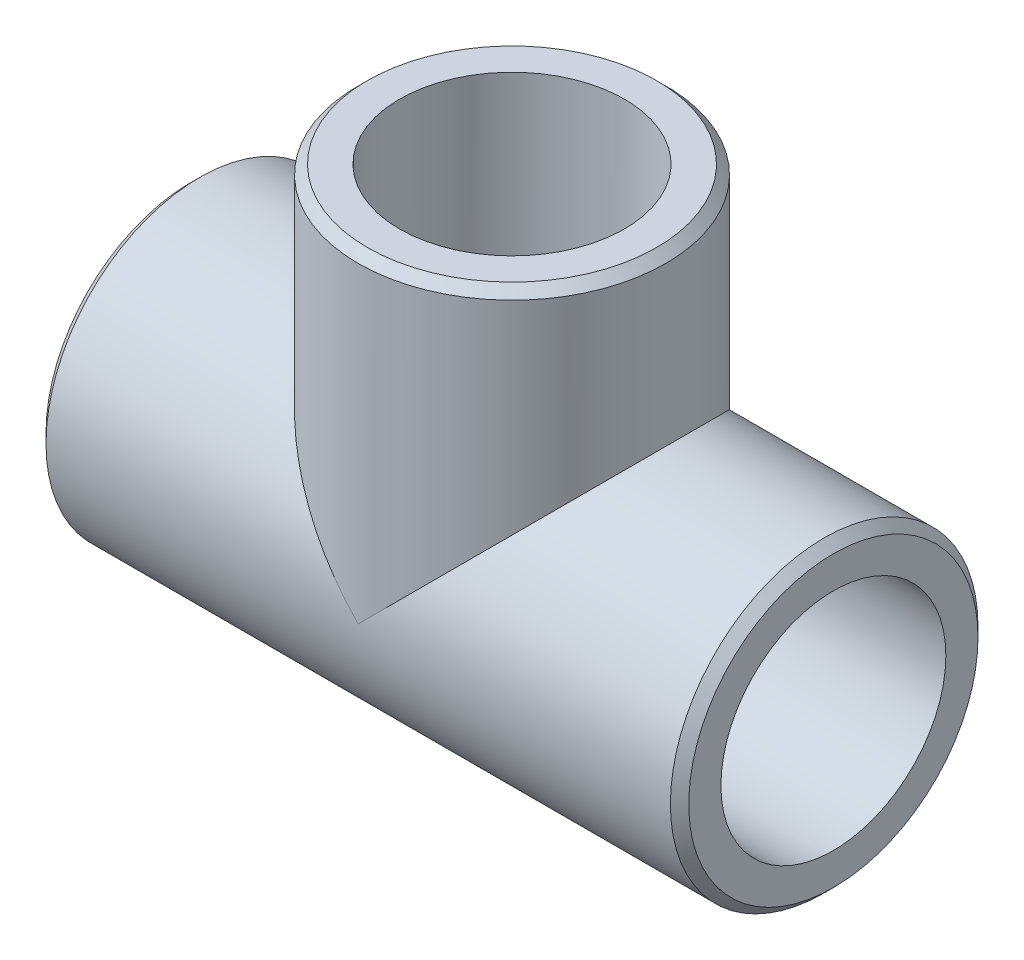
SolidWorks part; units mm, degrees
ref_plane "Спереди" through (0, 0, 0) normal (0, 0, 1) x (1, 0, 0)
ref_plane "Сверху" through (0, 0, 0) normal (0, 1, 0) x (1, 0, 0)
ref_plane "Справа" through (0, 0, 0) normal (1, 0, 0) x (0, 0, -1)
sketch "RunRoute" plane through (0, 0, 0) normal (1, 0, 0) x (0, 0, -1)
  circle A0 centre (0, 0) radius 16.75
  dimension "Diameter" = 33.5
extrude "RunExtrude" add sketch "RunRoute" along normal blind 35
mirror "RunExtrudeMirror" about plane through (0, 0, 0) normal (1, 0, 0) of "RunExtrude"
sketch "OutletRoute" plane through (0, 0, 0) normal (0, 1, 0) x (1, 0, 0)
  circle A0 centre (0, 0) radius 16.75
  dimension "Diameter" = 33.5
extrude "OutletExtrude" add sketch "OutletRoute" along normal blind 35
shell "TeeShell" thickness 4.5 removed face at (-35, 0, -16.75) removed face at (35, 0, -16.75) removed face at (0, 35, 16.75)
chamfer "TeeChamfer" distance 1 angle 45 3 edges at (35, 0, -16.75) (-35, 0, -16.75) (0, 35, 16.75)
sketch "Sketch1" plane through (0, 0, 0) normal (0, 0, 1) x (1, 0, 0)
  line L0 (-35, 0) -> (35, 0) construction
  line L1 (-35, 15.75) -> (-35, -15.75) construction
  line L2 (35, -15.75) -> (35, 15.75) construction
  line L3 (0, 0) -> (0, 35) construction
  line L4 (12.25, 35) -> (-12.25, 35) construction
other "CPoint1" parameters "Diameter"=25, "StubLength"=0
ref_axis "Axis1" through (45, 0, 0) along (-1, 0, 0)
other "CPoint2" parameters "Diameter"=25, "StubLength"=0
ref_axis "Axis2" through (0, 45, 0) along (0, -1, 0)
other "CPoint3" parameters "Diameter"=25, "StubLength"=0
ref_axis "Axis3" through (-45, 0, 0) along (1, 0, 0)
other "RPoint1"
